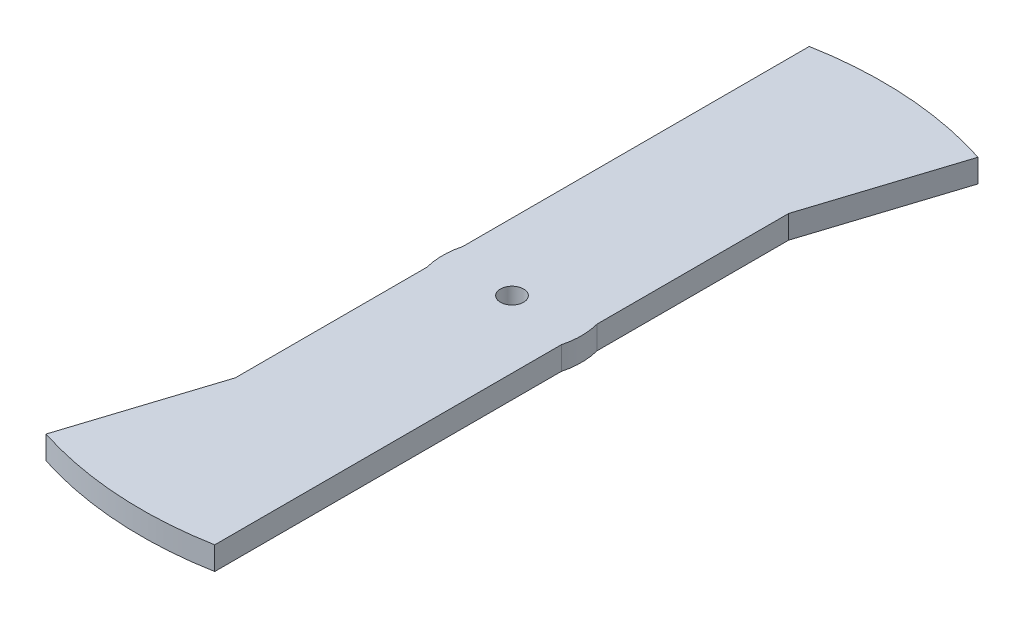
SolidWorks part; units mm, degrees
material "AISI 316 Stainless Steel Sheet (SS)"
ref_plane "Front Plane" through (0, 0, 0) normal (0, 0, 1) x (1, 0, 0)
ref_plane "Top Plane" through (0, 0, 0) normal (0, 1, 0) x (1, 0, 0)
ref_plane "Right Plane" through (0, 0, 0) normal (1, 0, 0) x (0, 0, -1)
sketch "Sketch1" plane through (0, 0, 0) normal (0, 1, 0) x (1, 0, 0)
  line L0 (0, 19.05) -> (0, 101.6) construction
  line L1 (-18.415, 99.9172) -> (-18.415, 4.8775)
  line L2 (18.415, 4.8775) -> (18.415, 57.4456)
  line L3 (18.415, 57.4456) -> (31.0147, 96.7504)
  line L4 (18.415, -99.9172) -> (18.415, -4.8775)
  line L5 (-18.415, -57.4456) -> (-31.0147, -96.7504)
  line L6 (-18.415, -4.8775) -> (-18.415, -57.4456)
  circle A0 centre (0, 0) radius 3.175
  circle A1 centre (0, 0) radius 19.05 construction
  circle A2 centre (0, 0) radius 101.6 construction
  arc A3 (-18.415, 99.9172) -> (31.0147, 96.7504) centre (0, 0) cw
  circle A4 centre (0, 0) radius 60.325 construction
  arc A5 (18.415, -99.9172) -> (-31.0147, -96.7504) centre (0, 0) cw
  arc A6 (-18.415, 4.8775) -> (-18.415, -4.8775) centre (0, 0) ccw
  arc A7 (18.415, 4.8775) -> (18.415, -4.8775) centre (0, 0) cw
  point P9 (18.415, 4.8775)
  point P15 (0, 60.325)
  point P23 (0, 0)
  dimension "D1" = 6.35
  dimension "D2" = 38.1
  dimension "D3" = 203.2
  dimension "D4" = 36.83
  dimension "D6" = 2
extrude "Boss-Extrude1" add sketch "Sketch1" along normal blind 6.35 contours A7 L2 L3 A3 L1 A6 L6 L5 A5 L4 A0 region at (6.36, 0, -99.2719)
